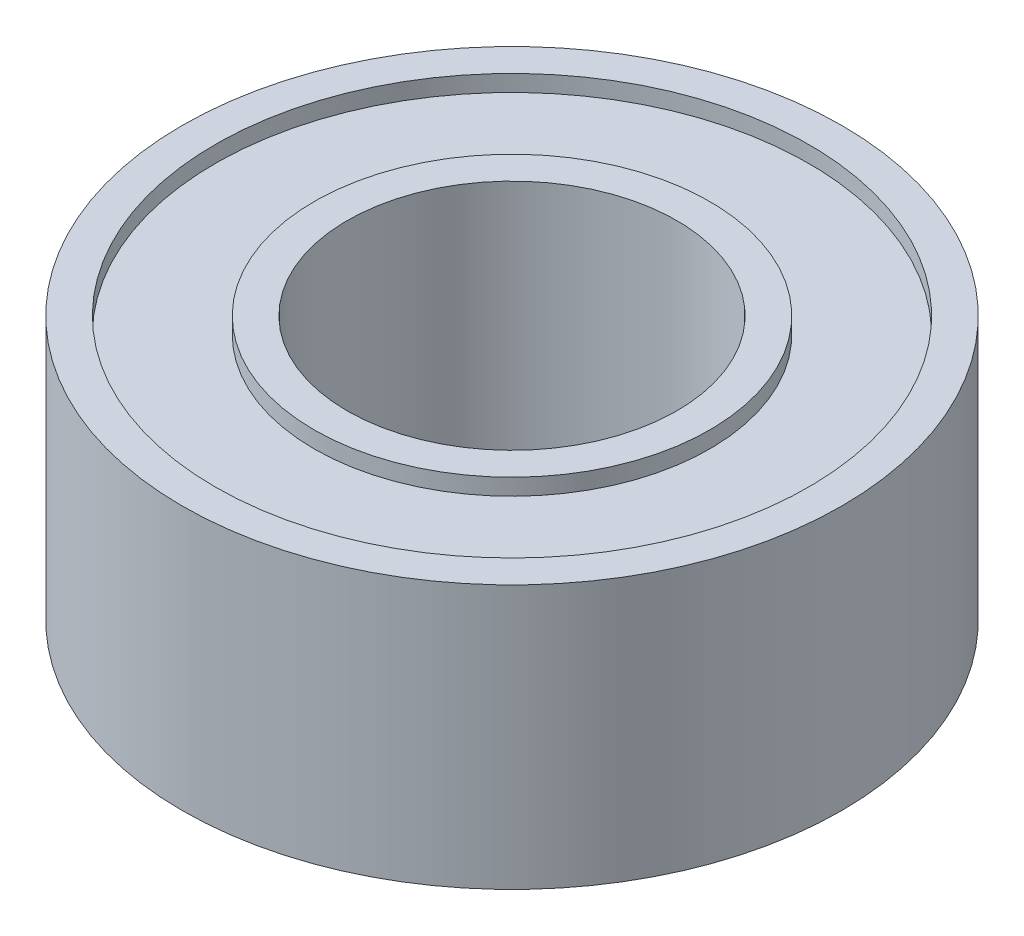
SolidWorks part; units mm, degrees
ref_plane "Front Plane" through (0, 0, 0) normal (0, 0, 1) x (1, 0, 0)
ref_plane "Top Plane" through (0, 0, 0) normal (0, 1, 0) x (1, 0, 0)
ref_plane "Right Plane" through (0, 0, 0) normal (1, 0, 0) x (0, 0, -1)
sketch "Sketch1" plane through (0, 0, 0) normal (0, 1, 0) x (1, 0, 0)
  circle A0 centre (0, 0) radius 2.5
  circle A1 centre (0, 0) radius 5
  circle A2 centre (0, 0) radius 3
  circle A3 centre (0, 0) radius 4.5
  dimension "D1" = 5
  dimension "D2" = 10
  dimension "D3" = 6
  dimension "D4" = 9
extrude "Boss-Extrude1" add sketch "Sketch1" along normal mid plane 4 contours A2 A0 | A1 A3 region at (-4.8586, 0, 0) region at (-2.9151, 0, 0)
extrude "Boss-Extrude2" add sketch "Sketch1<3>" along normal mid plane 3.5 contours A3 A2 region at (-4.3727, 0, 0)
sketch "Sketch1<3>" plane through (0, 0, 0) normal (0, 1, 0) x (1, 0, 0) same geometry as "Sketch1"
